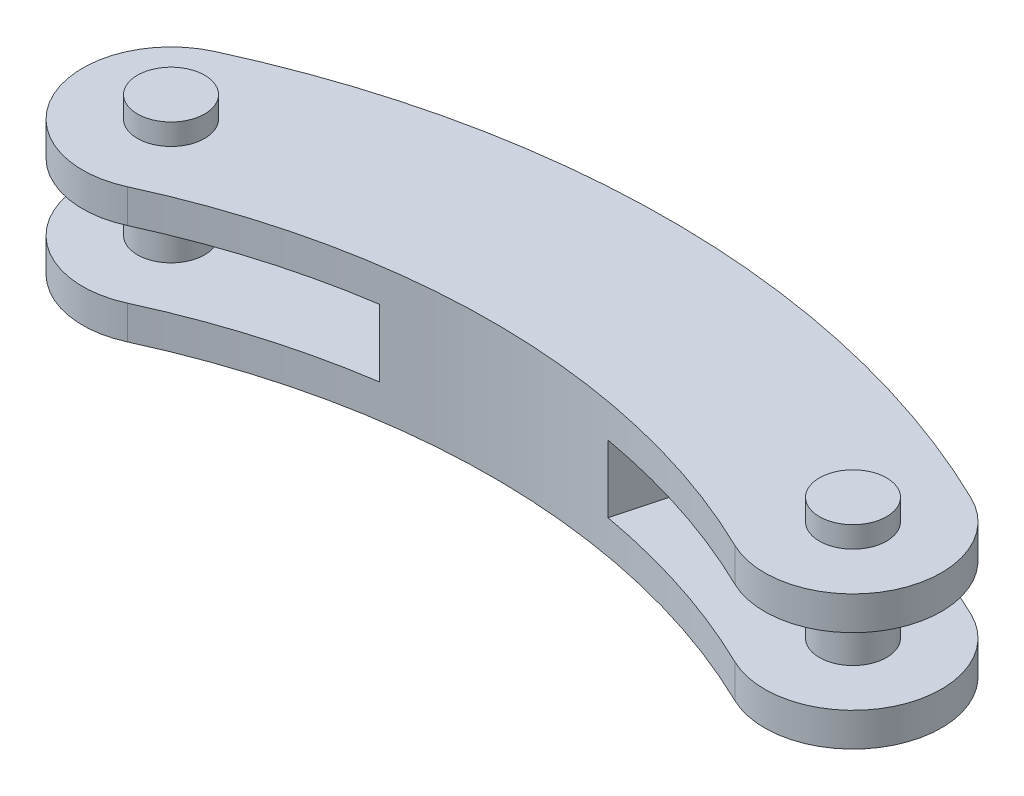
SolidWorks part; units mm, degrees
ref_plane "Front Plane" through (0, 0, 0) normal (0, 0, 1) x (1, 0, 0)
ref_plane "Top Plane" through (0, 0, 0) normal (0, 1, 0) x (1, 0, 0)
ref_plane "Right Plane" through (0, 0, 0) normal (1, 0, 0) x (0, 0, -1)
sketch "Sketch1" plane through (0, 0, 0) normal (0, 1, 0) x (1, 0, 0)
  line L0 (-98.2215, -20.7997) -> (96.7785, -22.9891) construction
  arc A0 (-98.2215, -20.7997) -> (96.7785, -22.9891) centre (-3.0354, -227.9798) cw construction
  arc A5 (107.723, -0.512) -> (-108.6586, 1.9174) centre (-3.0354, -227.9798) ccw
  arc A6 (85.834, -45.4661) -> (-87.7845, -43.5168) centre (-3.0354, -227.9798) ccw
  arc A7 (85.834, -45.4661) -> (107.723, -0.512) centre (96.7785, -22.9891) ccw
  arc A8 (-108.6586, 1.9174) -> (-87.7845, -43.5168) centre (-98.2215, -20.7997) ccw
  point P3 (-0.4757, 0.0058)
  dimension "D1" = 195
  dimension "D2" = 25
  dimension "D3" = 203
extrude "Boss-Extrude1" add sketch "Sketch1" along normal blind 9.5
sketch "Sketch2" plane through (0, 9.5, 0) normal (0, 1, 0) x (1, 0, 0)
  line L0 (0, -150) -> (0, 87.3967) construction
  line L1 (0, -150) -> (-45.9157, 21.3599)
  line L2 (0, -150) -> (45.9157, 21.3599)
  arc A0 (85.834, -45.4661) -> (-87.7845, -43.5168) centre (-3.0354, -227.9798) ccw construction
  arc A1 (107.723, -0.512) -> (-108.6586, 1.9174) centre (-3.0354, -227.9798) ccw construction
  arc A2 (85.834, -45.4661) -> (-87.7845, -43.5168) centre (-3.0354, -227.9798) ccw
  arc A3 (107.723, -0.512) -> (-108.6586, 1.9174) centre (-3.0354, -227.9798) ccw
  point P11 (45.9157, 21.3599)
  arc M4 (107.723, -0.512) -> (-108.6586, 1.9174) centre (-3.0354, -227.9798) ccw
  arc M6 (-87.7845, -43.5168) -> (85.834, -45.4661) centre (-3.0354, -227.9798) cw
  dimension "D1" = 15
  dimension "D2" = 150
extrude "Boss-Extrude2" add sketch "Sketch2" along normal blind 19 contours L0 A3 L1 M6 | L0 A2 L2 M4 region at (-19.9293, 9.5, -0.4853) region at (19.8085, 9.5, 0.0237)
sketch "Sketch3" plane through (0, 28.5, 0) normal (0, 1, 0) x (1, 0, 0)
  arc A4 (107.723, -0.512) -> (-108.6586, 1.9174) centre (-3.0354, -227.9798) ccw
  arc A5 (-108.6586, 1.9174) -> (-87.7845, -43.5168) centre (-98.2215, -20.7997) ccw
  arc A6 (85.834, -45.4661) -> (-87.7845, -43.5168) centre (-3.0354, -227.9798) ccw
  arc A7 (85.834, -45.4661) -> (107.723, -0.512) centre (96.7785, -22.9891) ccw
  arc A8 (107.723, -0.512) -> (-108.6586, 1.9174) centre (-3.0354, -227.9798) ccw
  arc A9 (-108.6586, 1.9174) -> (-87.7845, -43.5168) centre (-98.2215, -20.7997) ccw
  arc A10 (85.834, -45.4661) -> (-87.7845, -43.5168) centre (-3.0354, -227.9798) ccw
  arc A11 (85.834, -45.4661) -> (107.723, -0.512) centre (96.7785, -22.9891) ccw
  dimension "D1" = 0
extrude "Boss-Extrude3" add sketch "Sketch3" along normal blind 9.5
sketch "Sketch4" plane through (0, 38, 0) normal (0, 1, 0) x (1, 0, 0)
  circle A0 centre (-98.2215, -20.7997) radius 9.5
  circle A1 centre (96.7785, -22.9891) radius 9.5
  dimension "D1" = 19
extrude "Cut-Extrude1" cut sketch "Sketch4" against normal through all
extrude "Boss-Extrude4" add sketch "Sketch4<2>" against normal blind 50 from offset 6
sketch "Sketch4<2>" plane through (0, 38, 0) normal (0, 1, 0) x (1, 0, 0) same geometry as "Sketch4"
